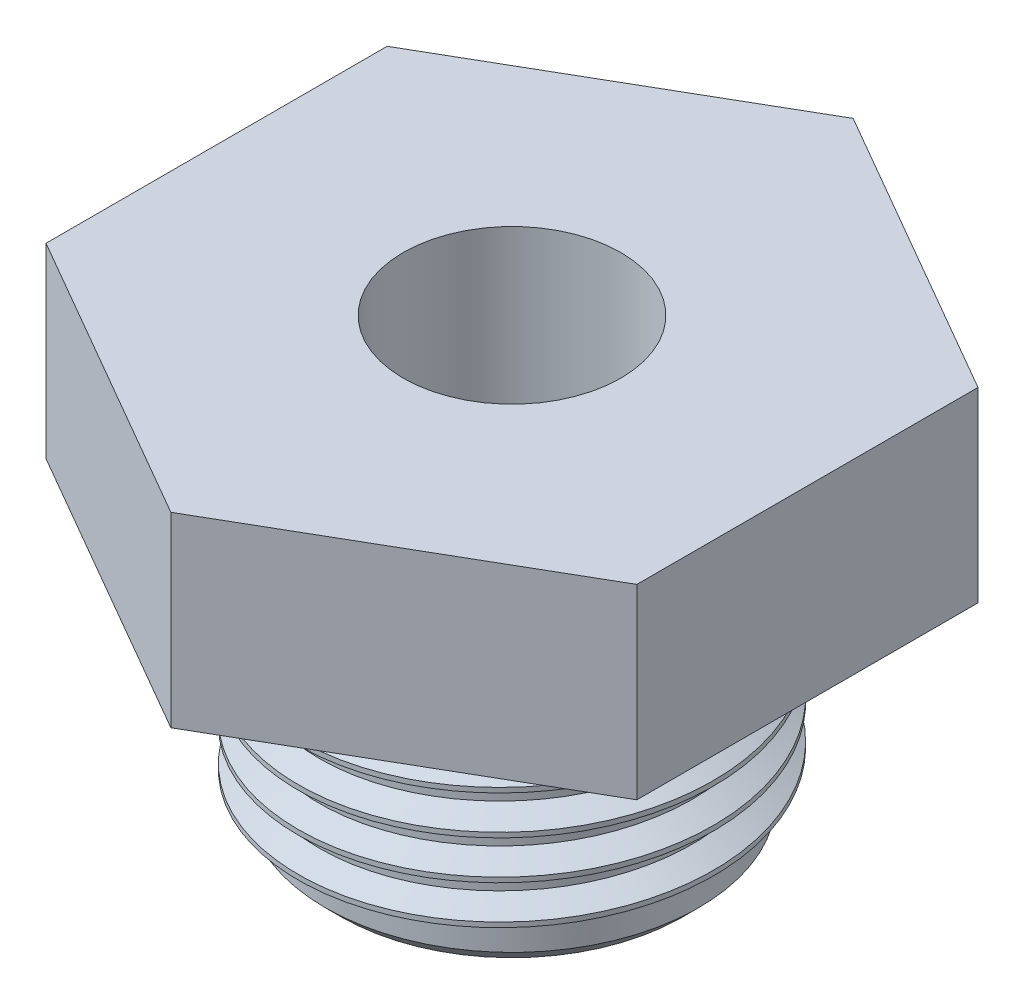
SolidWorks part; units mm, degrees
material "Aluminum Bronze"
ref_plane "Front Plane" through (0, 0, 0) normal (0, 0, 1) x (1, 0, 0)
ref_plane "Top Plane" through (0, 0, 0) normal (0, 1, 0) x (1, 0, 0)
ref_plane "Right Plane" through (0, 0, 0) normal (1, 0, 0) x (0, 0, -1)
sketch "Sketch2" plane through (0, 0, 0) normal (0, 1, 0) x (1, 0, 0)
  circle A0 centre (0, 0) radius 6
  dimension "D1" = 12
extrude "Boss-Extrude1" add sketch "Sketch2" along normal blind 8
sketch "Sketch3" plane through (0, 8, 0) normal (0, 1, 0) x (1, 0, 0)
  circle A0 centre (0, 0) radius 9.5
  dimension "D1" = 19
extrude "Boss-Extrude2" add sketch "Sketch3" along normal blind 6 contours A0
sketch "Sketch4" plane through (0, 14, 0) normal (0, 1, 0) x (1, 0, 0)
  line L1 (0, 10.9697) -> (-9.5, 5.4848)
  line L2 (-9.5, 5.4848) -> (-9.5, -5.4848)
  line L3 (-9.5, -5.4848) -> (0, -10.9697)
  line L4 (0, -10.9697) -> (9.5, -5.4848)
  line L5 (9.5, -5.4848) -> (9.5, 5.4848)
  line L6 (9.5, 5.4848) -> (0, 10.9697)
  circle A0 centre (0, 0) radius 9.5 construction
  circle A1 centre (0, 0) radius 10.9697
  point P10 (0, 10.9697)
  circle M7 centre (0, 0) radius 9.5
  dimension "D1" = 19
sketch "Sketch5" plane through (0, 14, 0) normal (0, 1, 0) x (1, 0, 0)
  circle A0 centre (0, 0) radius 3.5
extrude "Cut-Extrude2" cut sketch "Sketch5" against normal through all both and the other way through all
chamfer "Chamfer1" distance 0.5 angle 45 1 edges at (0, 0, 6)
thread "Thread2" pitch 1.25 method extrude profile "Thread Profile4" start angle 0, offset 0, length 6.5, pitch 1.25, diameter 12
ref_plane "Plane4" through (-6, 8, 0) normal (0, 0, 1) x (-1, 0, 0)
sketch "Thread Profile4" plane through (-6, 8, 0) normal (0, 0, 1) x (-1, 0, 0)
  line L0 (0, 0) -> (0, 1.25) construction
  line L1 (0, 0) -> (0.6766, 0.3906)
  line L2 (0.6766, 0.3906) -> (0.6766, 0.5469)
  line L3 (0.6766, 0.5469) -> (0, 0.9375)
  line L4 (0.6766, 0.4687) -> (0, 0.4687) construction
  line L11 (0, 0) -> (0, 0.9375)
  point P2 (0, 0)
  dimension "Pitch" = 1.25
  dimension "Profile_Angle" = 60
  dimension "Profile_Land" = 0.1562
  dimension "Profile_Height" = 0.6766
extrude "Boss-Extrude3" add sketch "Sketch4" against normal blind 6 contours L1 L2 M7 | L6 L1 M7 | L5 L6 M7 | L4 L5 M7 | L2 L3 M7 | L3 L4 M7 region at (0, 14, -9.8188) region at (-8.5034, 14, -4.9094) region at (8.5034, 14, -4.9094) region at (-8.5034, 14, 4.9094) region at (8.5034, 14, 4.9094) region at (0, 14, 9.8188)
